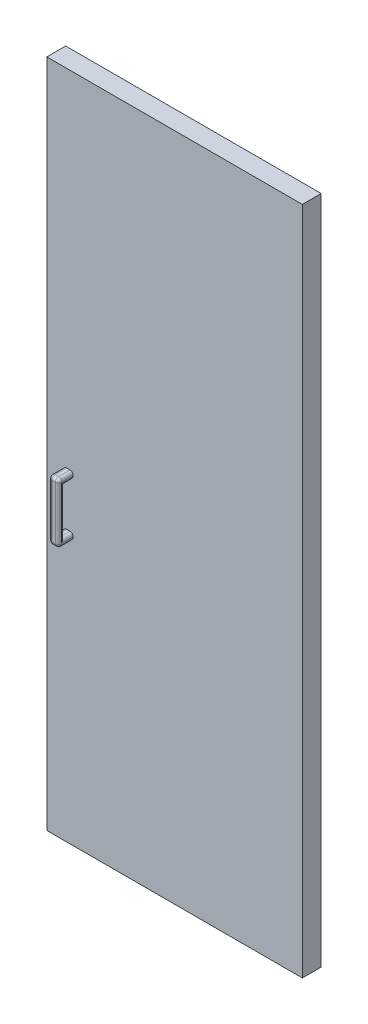
SolidWorks part; units mm, degrees
ref_plane "Front Plane" through (0, 0, 0) normal (0, 0, 1) x (1, 0, 0)
ref_plane "Top Plane" through (0, 0, 0) normal (0, 1, 0) x (1, 0, 0)
ref_plane "Right Plane" through (0, 0, 0) normal (1, 0, 0) x (0, 0, -1)
sketch "Sketch1" plane through (0, 0, 0) normal (0, 0, 1) x (1, 0, 0)
  line L0 (0, 0) -> (0, 18.7953) construction
  line L1 (0, 0) -> (0, 446.2018)
  line L2 (0, 446.2018) -> (-775, 446.2018)
  line L3 (-775, 446.2018) -> (-775, -1585.7982)
  line L4 (-775, -1585.7982) -> (0, -1585.7982)
  line L5 (0, -1585.7982) -> (0, 0)
  line L7 (-178.7641, -553.7982) -> (-148.7641, -553.7982)
  line L8 (-178.7641, -553.7982) -> (-178.7641, -735.7982)
  line L9 (-178.7641, -735.7982) -> (-148.7641, -735.7982)
  line L10 (-148.7641, -553.7982) -> (-148.7641, -735.7982)
  line L11 (-178.7641, -553.7982) -> (-148.7641, -735.7982) construction
  line L12 (-178.7641, -735.7982) -> (-148.7641, -553.7982) construction
  point P9 (-163.7641, -644.7982)
  dimension "D1" = 775
  dimension "D2" = 2032
  dimension "D3" = 30
  dimension "D4" = 182
  dimension "D5" = 850
extrude "Boss-Extrude2" add sketch "Sketch1" along normal blind 57.15 contours L3 L4 L5 L1 L2
sketch "Sketch3" plane through (0, 0, 57.15) normal (0, 0, 1) x (1, 0, 0)
sketch "Sketch4" plane through (0, 0, 57.15) normal (0, 0, 1) x (1, 0, 0)
  line L0 (-725, 0) -> (-725, -526.1226) construction
  line L1 (-775, 446.2018) -> (-775, -1585.7982) construction
  line L2 (-775, -1585.7982) -> (0, -1585.7982) construction
  line L3 (-725, -603.7982) -> (-695, -603.7982)
  line L4 (-725, -603.7982) -> (-725, -785.7982)
  line L5 (-725, -785.7982) -> (-695, -785.7982)
  line L6 (-695, -603.7982) -> (-695, -785.7982)
  point P8 (-710, -785.7982)
  dimension "D1" = 50
  dimension "D2" = 30
  dimension "D3" = 182
  dimension "D4" = 800
extrude "Boss-Extrude3" add sketch "Sketch4" along normal blind 44
sketch "Sketch5" plane through (-725, 0, 0) normal (-1, 0, 0) x (0, 0, 1)
  line L0 (57.15, -624.7982) -> (57.15, -764.7982)
  line L1 (57.15, -603.7982) -> (57.15, -785.7982) construction
  line L2 (57.15, -764.7982) -> (83.15, -764.7982)
  line L3 (83.15, -764.7982) -> (83.15, -624.7982)
  line L4 (83.15, -624.7982) -> (57.15, -624.7982)
  line L5 (101.15, -603.7982) -> (57.15, -603.7982) construction
  dimension "D1" = 21
  dimension "d2" = 140
  dimension "D3" = 26
extrude "Cut-Extrude1" cut sketch "Sketch5" against normal blind 57.15 contours L2 L3 L4 L0
fillet "Fillet1" radius 10 14 edges at (-725, -603.7982, 79.15) (-710, -603.7982, 101.15) (-695, -603.7982, 79.15) (-695, -624.7982, 70.15) (-725, -624.7982, 70.15) (-695, -694.7982, 83.15) (-695, -764.7982, 70.15) (-725, -694.7982, 83.15) (-725, -764.7982, 70.15) (-725, -694.7982, 101.15) (-725, -785.7982, 79.15) (-695, -785.7982, 79.15) (-695, -694.7982, 101.15) (-710, -785.7982, 101.15)
sketch "Sketch6" plane through (0, 0, 0) normal (0, 0, -1) x (-1, 0, 0)
  line L0 (775, 446.2018) -> (775, -1585.7982) construction
  line L1 (630, -924.7982) -> (750, -924.7982)
  line L2 (630, -924.7982) -> (630, -464.7982)
  line L3 (630, -464.7982) -> (750, -464.7982)
  line L4 (750, -924.7982) -> (750, -464.7982)
  line L5 (630, -924.7982) -> (750, -464.7982) construction
  line L6 (630, -464.7982) -> (750, -924.7982) construction
  line L7 (775, -1585.7982) -> (0, -1585.7982) construction
  point P0 (690, -694.7982)
  dimension "D1" = 25
  dimension "D2" = 891
  dimension "D3" = 120
  dimension "D4" = 460
extrude "Boss-Extrude4" add sketch "Sketch6" along normal blind 10
